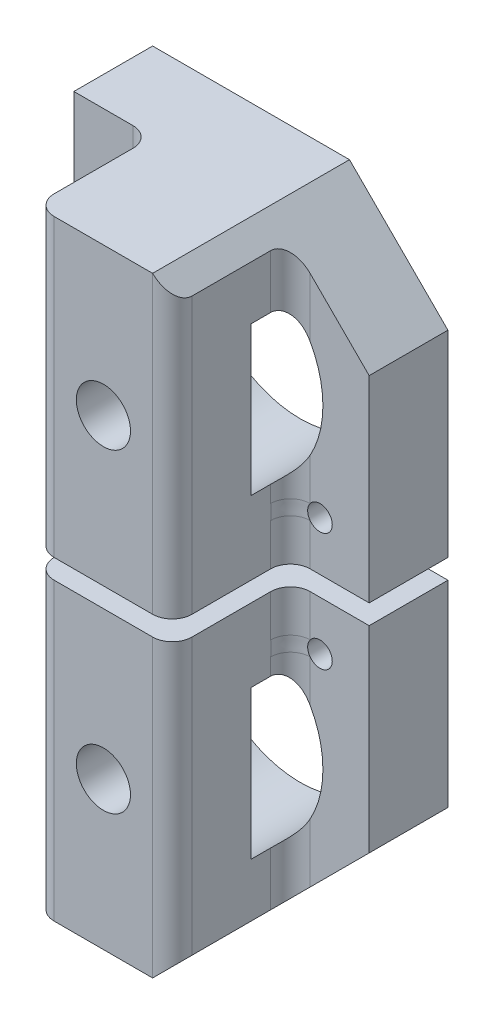
SolidWorks part; units mm, degrees
ref_plane "Front Plane" through (0, 0, 0) normal (0, 0, 1) x (1, 0, 0)
ref_plane "Top Plane" through (0, 0, 0) normal (0, 1, 0) x (1, 0, 0)
ref_plane "Right Plane" through (0, 0, 0) normal (1, 0, 0) x (0, 0, -1)
sketch "Sketch1" plane through (0, 0, 0) normal (0, 0, 1) x (1, 0, 0)
  line L0 (-15, -15) -> (5, -15)
  line L1 (5, -15) -> (15, -5)
  line L2 (-15, -15) -> (-15, 15)
  line L3 (-15, 15) -> (15, 15)
  line L4 (15, -5) -> (15, 15)
  line L5 (-15, -15) -> (15, 15) construction
  line L6 (-15, 15) -> (15, -15) construction
  circle A0 centre (-10, 10) radius 1.25
  circle A1 centre (10, 10) radius 1.25
  circle A2 centre (-10, -10) radius 1.25
  point P0 (0, 0)
  point P11 (0, 0)
  point P14 (0, 0)
  dimension "D3" = 2.5
  dimension "D6" = 20
  dimension "D1" = 30
  dimension "D2" = 30
  dimension "D4" = 20
  dimension "D5" = 135
extrude "Main" add sketch "Sketch1" along normal blind 20
sketch "Sketch2" plane through (0, 0, 0) normal (0, 0, 1) x (1, 0, 0)
  line L0 (-15, -15) -> (15, 15) construction
  line L1 (-15, 15) -> (15, -15) construction
  line L2 (15, -5) -> (15, 15) construction
  line L3 (15, 15) -> (-15, 15) construction
  circle A0 centre (0, 0) radius 10.3
  dimension "D1" = 20.6
extrude "CentralHole" cut sketch "Sketch2" along normal blind 12
sketch "Sketch5" plane through (0, 0, 20) normal (0, 0, 1) x (1, 0, 0)
  line L0 (15, 15) -> (-15, 15) construction
  line L1 (15, -15) -> (7, -15)
  line L2 (15, -15) -> (15, 15)
  line L3 (15, 15) -> (7, 15)
  line L4 (7, -15) -> (7, 15)
  line L5 (-15, -15) -> (5, -15) construction
  line L6 (-15, -15) -> (-7, -15)
  line L7 (-15, -15) -> (-15, 15)
  line L8 (-15, 15) -> (-7, 15)
  line L9 (-7, -15) -> (-7, 15)
  line L10 (15, -5) -> (15, 15) construction
  circle A0 centre (0, 0) radius 2.75
  dimension "D3" = 5.5
  dimension "D1" = 8
  dimension "D2" = 8
extrude "Cut-Extrude3" cut sketch "Sketch5" against normal blind 12
fillet "Fillet1" radius 2 6 edges at (-7, 0, 20) (7, 1, 20) (-7, -11.2779, 8) (-7, 11.2779, 8) (7, 11.2779, 8) (7, -10.2779, 8)
ref_plane "Plane1" through (0, 16, 0) normal (0, 1, 0) x (1, 0, 0)
mirror "Mirror1" about plane through (0, 16, 0) normal (0, 1, 0) of bodies 104
